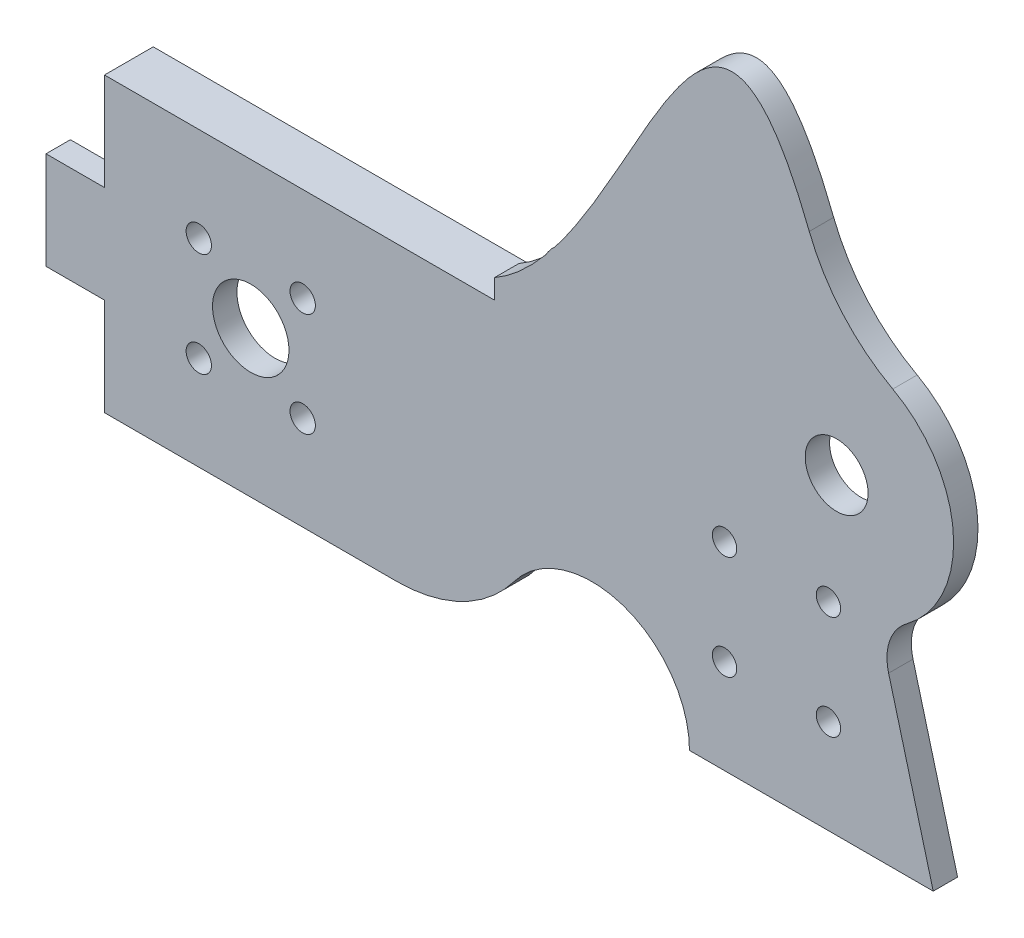
SolidWorks part; units mm, degrees
ref_plane "Front Plane" through (0, 0, 0) normal (0, 0, 1) x (1, 0, 0)
ref_plane "Top Plane" through (0, 0, 0) normal (0, 1, 0) x (1, 0, 0)
ref_plane "Right Plane" through (0, 0, 0) normal (1, 0, 0) x (0, 0, -1)
sketch "Sketch1" plane through (0, 0, 0) normal (0, 0, 1) x (1, 0, 0)
  line L0 (0, 0) -> (107.95, 0)
  line L3 (0, 38.1) -> (0, 25.4)
  line L4 (95.3675, 55.88) -> (0, 38.1)
  line L5 (0, 19.05) -> (100.2273, 19.05) construction
  line L6 (19.05, 19.05) -> (19.05, 28.62) construction
  line L7 (19.05, 19.05) -> (25.817, 25.817) construction
  line L8 (107.95, 0) -> (100.9363, 26.1756)
  line L10 (0, 12.7) -> (0, 0)
  line L11 (0, 25.4) -> (-7.62, 25.4)
  line L13 (0, 12.7) -> (-7.62, 12.7)
  line L14 (-7.62, 25.4) -> (-7.62, 12.7)
  line L15 (100.9363, 26.1756) -> (100.8688, 26.4276)
  arc A0 (100.8688, 26.4276) -> (95.3675, 55.88) centre (95.3675, 40.64) ccw
  circle A1 centre (95.3675, 40.64) radius 4.0957
  circle A2 centre (19.05, 19.05) radius 9.57 construction
  circle A3 centre (25.817, 25.817) radius 1.651
  circle A4 centre (25.817, 12.283) radius 1.651
  circle A5 centre (12.283, 12.283) radius 1.651
  circle A6 centre (12.283, 25.817) radius 1.651
  point P26 (19.05, 19.05)
  dimension "D1" = 8.1915
  dimension "D5" = 15.24
  dimension "D4" = 19.14
  dimension "D7" = 3.302
  dimension "D11" = 97.0107
  dimension "D2" = 38.1
  dimension "D3" = 40.64
  dimension "D6" = 107.95
  dimension "D8" = 45
  dimension "D9" = 4
  dimension "D10" = 19.05
  dimension "D12" = 75
  dimension "D14" = 12.7
  dimension "D15" = 12.7
  dimension "D16" = 7.62
extrude "Boss-Extrude1" add sketch "Sketch1" along normal blind 3.175
sketch "Sketch2" plane through (0, 0, 3.175) normal (0, 0, 1) x (1, 0, 0)
  circle A0 centre (95.3675, 40.64) radius 38.1 construction
sketch "Sketch6" plane through (0, 0, 3.175) normal (0, 0, 1) x (1, 0, 0)
  line L0 (0, 0) -> (107.95, 0) construction
  line L1 (50.8, 0) -> (76.2, 0)
  arc A0 (76.2, 0) -> (50.8, 0) centre (63.5, 0) ccw
  dimension "D1" = 25.4
  dimension "D2" = 31.75
extrude "Cut-Extrude2" cut sketch "Sketch6" against normal blind 6.35
sketch "Sketch7" plane through (0, 0, 3.175) normal (0, 0, 1) x (1, 0, 0)
  line L0 (12.283, 25.817) -> (25.817, 12.283) construction
  line L1 (12.283, 12.283) -> (25.817, 25.817) construction
  line L2 (12.283, 25.817) -> (78.4839, 25.817) construction
  line L3 (11.7326, 12.283) -> (12.283, 12.283) construction
  circle A0 centre (19.05, 19.05) radius 4.9784
  circle A4 centre (80.7666, 12.283) radius 1.5875
  circle A5 centre (94.2997, 12.283) radius 1.5875
  circle A6 centre (80.7666, 25.817) radius 1.5875
  circle A7 centre (94.2997, 25.817) radius 1.5875
  dimension "D1" = 9.9568
  dimension "D2" = 3.175
  dimension "D3" = 13.5331
extrude "Cut-Extrude3" cut sketch "Sketch7" against normal through all
fillet "Fillet1" radius 6.35 1 edges at (100.8688, 26.4276, 1.5875)
sketch "Sketch8" plane through (0, 0, 3.175) normal (0, 0, 1) x (1, 0, 0)
  line L1 (0, 38.1) -> (50.8, 38.1)
  line L2 (0, 38.1) -> (0, 50.8)
  line L3 (0, 50.8) -> (50.8, 50.8)
  line L4 (50.8, 38.1) -> (50.8, 50.8)
  dimension "D1" = 50.8
  dimension "D2" = 12.7
extrude "Cut-Extrude4" cut sketch "Sketch8" against normal blind 50.8
sketch "Sketch9" plane through (0, 0, 3.175) normal (0, 0, 1) x (1, 0, 0)
  line L3 (50.8, 40.64) -> (57.15, 40.64)
  line L5 (57.15, 40.64) -> (50.8, 40.64)
  line L6 (57.15, 40.64) -> (57.15, 50.8)
  line L7 (57.15, 50.8) -> (50.8, 50.8)
  line L8 (50.8, 40.64) -> (50.8, 50.8)
  line L9 (0, 38.1) -> (50.8, 38.1) construction
  line M8 (50.8, 47.571) -> (50.8, 38.1)
  line M21 (95.3675, 55.88) -> (50.8, 47.571)
  dimension "D1" = 10.16
  dimension "D2" = 2.54
  dimension "D3" = 6.35
extrude "Cut-Extrude5" cut sketch "Sketch9" against normal blind 19.304 contours L3 L6 M21 M8 region at (54.0583, 44.4092, 3.175)
fillet "Fillet6" radius 6.35 1 edges at (57.15, 40.64, 1.5875)
fillet "Fillet7" radius 6.35 1 edges at (57.15, 48.7549, 1.5875)
fillet "Fillet8" radius 19.05 1 edges at (50.8, 0, 1.5875)
sketch "Sketch12" plane through (0, 0, 3.175) normal (0, 0, 1) x (1, 0, 0)
  line L0 (107.95, 0) -> (146.812, 0) construction
  line L1 (8.0257, 45.4128) -> (80.6683, 75.7903) construction
  line L2 (95.3675, 40.64) -> (80.6683, 75.7903) construction
  line L3 (80.6683, 75.7903) -> (79.4434, 78.7195) construction
  line L4 (50.8, 40.64) -> (85.0271, 40.64)
  line L5 (85.0271, 40.64) -> (95.3675, 55.88)
  arc A0 (61.8128, 49.6242) -> (56.8883, 45.1859) centre (62.9766, 43.3817) ccw construction
  circle A1 centre (19.05, 19.05) radius 28.575 construction
  circle A2 centre (95.3675, 40.64) radius 38.1 construction
  circle A3 centre (80.6683, 75.7903) radius 3.175 construction
  spline S0 degree 3 poles (50.8, 40.64) (70.7778, 52.1788) (78.5943, 111.5434) (95.3675, 55.88) knots 0 0 0 0 1 1 1 1
  dimension "D2" = 6.35
  dimension "D1" = 38.862
extrude "Boss-Extrude2" add sketch "Sketch12" against normal blind 3.175
fillet "Fillet9" radius 24.13 1 edges at (95.3675, 55.88, 1.5875)
sketch "Sketch13" plane through (0, 0, 0) normal (0, 0, -1) x (-1, 0, 0)
  line L0 (0, 38.1) -> (0, 25.4) construction
  line L1 (-50.8, 38.1) -> (0, 38.1)
  line L2 (-50.8, 38.1) -> (-50.8, 28.4023)
  line L3 (-50.8, 28.4023) -> (0, 28.4023)
  line L4 (0, 38.1) -> (0, 28.4023)
  line L5 (0, 12.7) -> (0, 0) construction
  line L6 (0, 8.5046) -> (-38.1, 8.5046)
  line L7 (0, 8.5046) -> (0, 0)
  line L8 (0, 0) -> (-38.1, 0)
  line L9 (-38.1, 8.5046) -> (-38.1, 0)
extrude "Boss-Extrude3" add sketch "Sketch13" along normal blind 3.175
